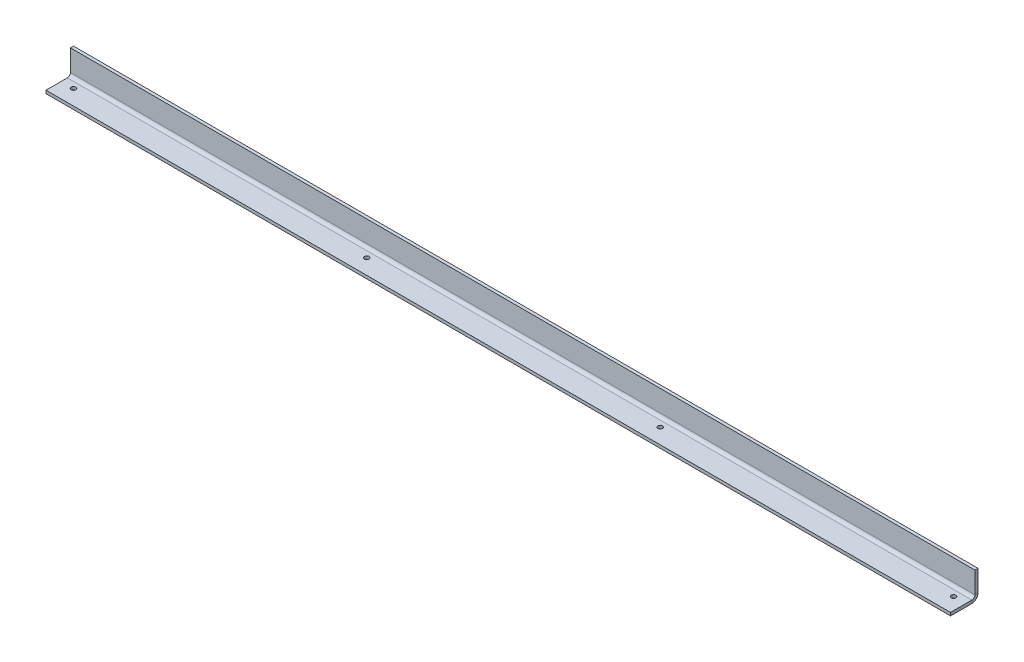
SolidWorks part; units mm, degrees
note: The reader was unsure of these and kept them because the rebuilt part matched: thickness of "Base-Flange1", "Edge-Flange1", "Sheet-Metal1", "Sheet-Metal2", "Sheet-Metal3", "Sheet-Metal4"; flange length of "Edge-Flange1".
material "Pine"
ref_plane "Front Plane" through (0, 0, 0) normal (0, 0, 1) x (1, 0, 0)
ref_plane "Top Plane" through (0, 0, 0) normal (0, 1, 0) x (1, 0, 0)
ref_plane "Right Plane" through (0, 0, 0) normal (1, 0, 0) x (0, 0, -1)
sketch "Sketch1" plane through (0, 0, 0) normal (0, 1, 0) x (1, 0, 0)
  line L1 (469.9, -14.2875) -> (-469.9, -14.2875)
  line L2 (469.9, -14.2875) -> (469.9, 14.2875)
  line L3 (469.9, 14.2875) -> (-469.9, 14.2875)
  line L4 (-469.9, -14.2875) -> (-469.9, 14.2875)
  line L5 (469.9, -14.2875) -> (-469.9, 14.2875) construction
  line L6 (469.9, 14.2875) -> (-469.9, -14.2875) construction
  point P0 (0, 0)
  dimension "D1" = 939.8
  dimension "D2" = 28.575
base flange "Base-Flange1" sketch "Sketch1" thickness 3.175 reverse thickness direction no parameters "D1"=3.175
edge flange "Edge-Flange1" sketch "Sketch8" flange angle 90 flange length 28.575 flange position material inside bend radius 3.175 thickness 3.175 relief rectangular parameters "D1"=2.032, "D6"=10
sketch "Sketch8" plane through (0, 0, -14.2875) normal (0, 0, 1) x (1, 0, 0)
  line L2 (-469.9, 0) -> (-469.9, 25.4)
  line L3 (-469.9, 25.4) -> (469.9, 25.4)
  line L4 (469.9, 25.4) -> (469.9, 0)
  line L5 (469.9, 0) -> (-469.9, 0) construction
  line L6 (469.9, 0) -> (-469.9, 0)
bend "EdgeBend1" bend radius 3.175 bend angle 90 parameters "D5"=1
fillet "Fillet1" [suppressed] radius 12.7
hole_wizard "#11 (0.191) Diameter Hole1" positions "Sketch11" profile "Sketch12" hole size "#11" standard "ANSI Inch" end condition through all
sketch "Sketch11" plane through (0, 0, 0) normal (0, 1, 0) x (1, 0, 0)
  line L0 (-469.9, 7.9375) -> (-469.9, -14.2875) construction
  line L1 (469.9, 14.2875) -> (-469.9, 14.2875) construction
  point P0 (-457.2, 1.5875)
  dimension "D1" = 12.7
  dimension "D2" = 12.7
sketch "Sketch12" plane through (-457.2, 0, -1.5875) normal (1, 0, 0) x (0, 0, 1)
  line L0 (0, 0) -> (0, 3.175)
  line L1 (0, 3.175) -> (2.4257, 3.175)
  line L2 (2.4257, 3.175) -> (2.4257, 0)
  line L5 (2.4257, 0) -> (0, 0)
  line L11 (0, -6.35) -> (0, 107.95) construction
  dimension "Thru Hole Dia." = 4.8514
  dimension "Thru Hole Depth" = 3.175
pattern_linear "LPattern1" count 4 spacing 304.8 along (1, 0, 0) of "#11 (0.191) Diameter Hole1"
sketch "Bend-Lines1" [suppressed] plane through (0, 0, 0) normal (0, 1, 0) x (1, 0, 0)
sketch "Bounding-Box1" [suppressed] plane through (0, 0, 0) normal (0, 1, 0) x (1, 0, 0)
sheet metal parameters "Sheet-Metal1" thickness 3.175 parameters "D1"=2.032, "D7"=2.0066
flat pattern "Flat-Pattern1" [suppressed]
sketch "Bend-Lines2" plane through (0, 0, 0) normal (0, 1, 0) x (1, 0, 0)
sketch3d "Bounding-Box2" [suppressed]
  line L0 (-469.9, -14.2875, 0) -> (469.9, -14.2875, 0) construction
  line L1 (-469.9, 14.2875, 0) -> (469.9, 14.2875, 0) construction
  line L2 (-469.9, -14.2875, 0) -> (-469.9, 14.2875, 0) construction
  line L3 (469.9, -14.2875, 0) -> (469.9, 14.2875, 0) construction
sheet metal parameters "Sheet-Metal2" thickness 3.175 parameters "D1"=2.032, "D7"=2.0066
flat pattern "Flat-Pattern1"
sketch "Bend-Lines2" plane through (0, 0, 0) normal (0, 1, 0) x (1, 0, 0)
  line L0 (469.9, 12.6328) -> (-469.9, 12.6328) construction
  line L1 (469.9, 12.6328) -> (-469.9, 12.6328) construction
sketch3d "Bounding-Box2" [suppressed]
  line L0 (-469.9, -14.2875, 0) -> (469.9, -14.2875, 0) construction
  line L1 (-469.9, 39.5531, 0) -> (469.9, 39.5531, 0) construction
  line L2 (-469.9, -14.2875, 0) -> (-469.9, 39.5531, 0) construction
  line L3 (469.9, -14.2875, 0) -> (469.9, 39.5531, 0) construction
bend of the flat pattern "Flatten-<EdgeBend1>1"
sheet metal parameters "Sheet-Metal3" thickness 3.175 parameters "D1"=2.032, "D7"=2.0066
flat pattern "Flat-Pattern1"
sketch "Bend-Lines2" plane through (0, 0, 0) normal (0, 1, 0) x (1, 0, 0)
  line L0 (469.9, 12.6328) -> (-469.9, 12.6328) construction
  line L1 (469.9, 12.6328) -> (-469.9, 12.6328) construction
sketch3d "Bounding-Box2" [suppressed]
  line L0 (-469.9, -14.2875, 0) -> (469.9, -14.2875, 0) construction
  line L1 (-469.9, 39.5531, 0) -> (469.9, 39.5531, 0) construction
  line L2 (-469.9, -14.2875, 0) -> (-469.9, 39.5531, 0) construction
  line L3 (469.9, -14.2875, 0) -> (469.9, 39.5531, 0) construction
bend of the flat pattern "Flatten-<EdgeBend1>1"
sheet metal parameters "Sheet-Metal4" thickness 3.175 parameters "D1"=2.032, "D7"=2.0066
flat pattern "Flat-Pattern1"
sketch "Bend-Lines2" plane through (0, 0, 0) normal (0, 1, 0) x (1, 0, 0)
  line L0 (469.9, 11.678) -> (-469.9, 11.678) construction
  line L1 (469.9, 11.678) -> (-469.9, 11.678) construction
sketch3d "Bounding-Box2" [suppressed]
  line L0 (469.9, -14.2875, 0) -> (-469.9, -14.2875, 0) construction
  line L1 (469.9, 37.6434, 0) -> (-469.9, 37.6434, 0) construction
  line L2 (469.9, -14.2875, 0) -> (469.9, 37.6434, 0) construction
  line L3 (-469.9, -14.2875, 0) -> (-469.9, 37.6434, 0) construction
bend of the flat pattern "Flatten-<EdgeBend1>1"
